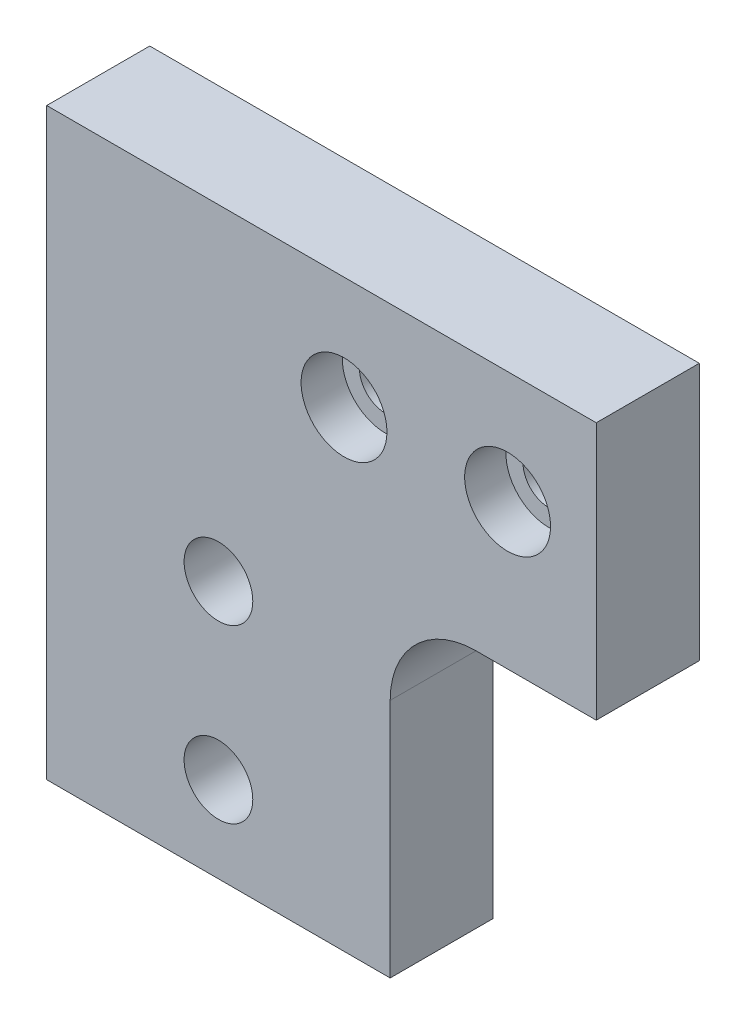
SolidWorks part; units mm, degrees
ref_plane "Plano frontal" through (0, 0, 0) normal (0, 0, 1) x (1, 0, 0)
ref_plane "Plano superior" through (0, 0, 0) normal (0, 1, 0) x (1, 0, 0)
ref_plane "Plano direito" through (0, 0, 0) normal (1, 0, 0) x (0, 0, -1)
sketch "Esboço1" plane through (0, 0, 0) normal (0, 0, 1) x (1, 0, 0)
  line L1 (-16, 17) -> (16, 17)
  line L2 (-16, 17) -> (-16, -17)
  line L3 (-16, -17) -> (16, -17)
  line L4 (16, 17) -> (16, -17)
  line L5 (-16, 17) -> (16, -17) construction
  line L6 (-16, -17) -> (16, 17) construction
  point P0 (0, 0)
  dimension "D1" = 32
  dimension "D2" = 34
extrude "Ressalto-extrusão1" add sketch "Esboço1" along normal blind 6
sketch "Esboço2" plane through (0, 0, 6) normal (0, 0, 1) x (1, 0, 0)
  line L1 (16, -17) -> (4, -17)
  line L2 (16, -17) -> (16, 2)
  line L3 (16, 2) -> (4, 2)
  line L4 (4, -17) -> (4, 2)
  line L5 (-16, -17) -> (16, -17) construction
  line L6 (-6, 17) -> (-6, -17)
  line L7 (-6, 17) -> (-6, -17) construction
  line L8 (16, 17) -> (-16, 17) construction
  circle A0 centre (-6, -12) radius 2
  circle A1 centre (-6, -2) radius 2
  dimension "D4" = 4
  dimension "D1" = 12
  dimension "D2" = 15
  dimension "D5" = 5
  dimension "D6" = 10
  dimension "D3" = 10
extrude "Corte-extrusão1" cut sketch "Esboço2" against normal up to surface (6 mm away) up to face at (0, 0, 0)
fillet "Filete1" radius 5 1 edges at (4, 2, 3)
sketch "Esboço5" plane through (0, 0, 0) normal (0, 0, -1) x (-1, 0, 0)
  circle A0 centre (-10.8375, 10.4375) radius 1.175 construction
  circle A1 centre (-1.3125, 10.4375) radius 1.175 construction
  circle A2 centre (-10.8375, 10.4375) radius 1.175 construction
  circle A3 centre (-1.3125, 10.4375) radius 1.175 construction
  circle A4 centre (-10.8375, 10.4375) radius 1.5
  circle A5 centre (-1.3125, 10.4375) radius 1.5
  dimension "D1" = 3
extrude "Corte-extrusão3" cut sketch "Esboço5" against normal up to surface (6 mm away) up to face at (2.2806, 0.2908, 6)
sketch "Esboço8" plane through (0, 0, 6) normal (0, 0, 1) x (1, 0, 0)
  circle A0 centre (10.8375, 10.4375) radius 2.5
  circle A1 centre (1.3125, 10.4375) radius 2.5
  dimension "D1" = 5
extrude "Corte-extrusão6" cut sketch "Esboço8" against normal blind 2.4
